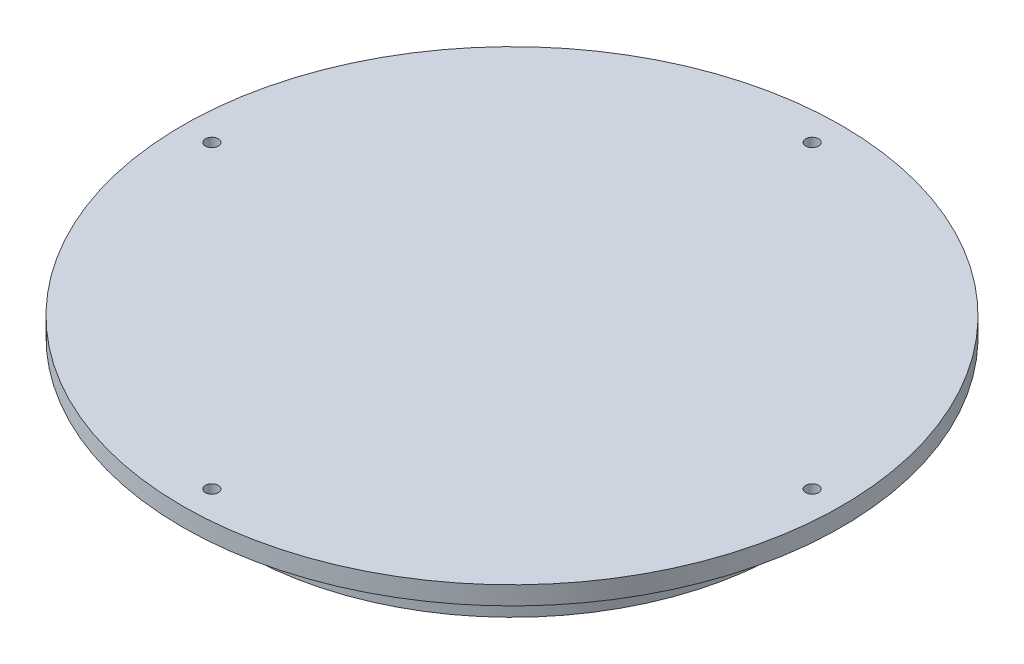
SolidWorks part; units mm, degrees
material "PLA+"
ref_plane "Front Plane" through (0, 0, 0) normal (0, 0, 1) x (1, 0, 0)
ref_plane "Top Plane" through (0, 0, 0) normal (0, 1, 0) x (1, 0, 0)
ref_plane "Right Plane" through (0, 0, 0) normal (1, 0, 0) x (0, 0, -1)
sketch "Sketch1" plane through (0, 0, 0) normal (0, 1, 0) x (1, 0, 0)
  circle A0 centre (0, 0) radius 64
  circle A1 centre (0, 0) radius 61
  circle A2 centre (0, 0) radius 90
  dimension "D1" = 128
  dimension "D2" = 122
  dimension "D3" = 180
extrude "Boss-Extrude1" add sketch "Sketch1" along normal blind 18 contours A2 A0 region at (-87.4544, 0, 0)
sketch "Sketch2" plane through (0, 18, 0) normal (0, 1, 0) x (1, 0, 0)
  circle A0 centre (0, 0) radius 90
extrude "Boss-Extrude2" add sketch "Sketch2" along normal blind 1
sketch "Sketch3" plane through (0, 0, 0) normal (0, -1, 0) x (1, 0, 0)
  circle A0 centre (0, 0) radius 74
  circle A1 centre (0, 0) radius 90
  circle A2 centre (0, 0) radius 64 construction
  dimension "D1" = 10
extrude "Cut-Extrude1" cut sketch "Sketch3" against normal blind 14
sketch "Sketch4" plane through (0, 0, 0) normal (0, -1, 0) x (1, 0, 0)
  line L0 (5, 66.5) -> (-5, 66.5)
  line L1 (-66.5, 5) -> (-61.5, 5)
  line L2 (-66.5, 5) -> (-66.5, -5)
  line L3 (-66.5, -5) -> (-61.5, -5)
  line L4 (-61.5, 5) -> (-61.5, -5)
  line L5 (-66.5, 5) -> (-61.5, -5) construction
  line L6 (-66.5, -5) -> (-61.5, 5) construction
  line L7 (5, 66.5) -> (5, 61.5)
  line L8 (5, 61.5) -> (-5, 61.5)
  line L9 (-5, 66.5) -> (-5, 61.5)
  line L10 (66.5, -5) -> (66.5, 5)
  line L11 (66.5, -5) -> (61.5, -5)
  line L12 (61.5, -5) -> (61.5, 5)
  line L13 (66.5, 5) -> (61.5, 5)
  line L14 (-5, -66.5) -> (5, -66.5)
  line L15 (-5, -66.5) -> (-5, -61.5)
  line L16 (-5, -61.5) -> (5, -61.5)
  line L17 (5, -66.5) -> (5, -61.5)
  circle A0 centre (0, 0) radius 64 construction
  circle A1 centre (0, 0) radius 64 construction
  point P0 (-64, 0)
  point P24 (0, 0)
  dimension "D1" = 5
  dimension "D2" = 10
  dimension "D3" = 4
extrude "Boss-Extrude3" add sketch "Sketch4" against normal blind 2
fillet "Fillet1" radius 2 16 edges at (-5, 1, -61.5) (0, 2, -61.5) (5, 1, -61.5) (0, 0, -61.5) (61.5, 1, -5) (61.5, 2, 0) (61.5, 1, 5) (61.5, 0, 0) (-61.5, 1, 5) (-61.5, 2, 0) (-61.5, 1, -5) (-61.5, 0, 0) (5, 1, 61.5) (0, 2, 61.5) (-5, 1, 61.5) (0, 0, 61.5)
sketch "Sketch5" plane through (0, 14, 0) normal (0, -1, 0) x (1, 0, 0)
  circle A0 centre (0, 81.9693) radius 1.75
  circle A1 centre (81.9693, 0) radius 1.75
  circle A2 centre (0, -81.9693) radius 1.75
  circle A3 centre (-81.9693, 0) radius 1.75
  point P11 (0, 0)
  dimension "D1" = 3.5
  dimension "D2" = 4
extrude "Cut-Extrude2" cut sketch "Sketch5" against normal blind 75
